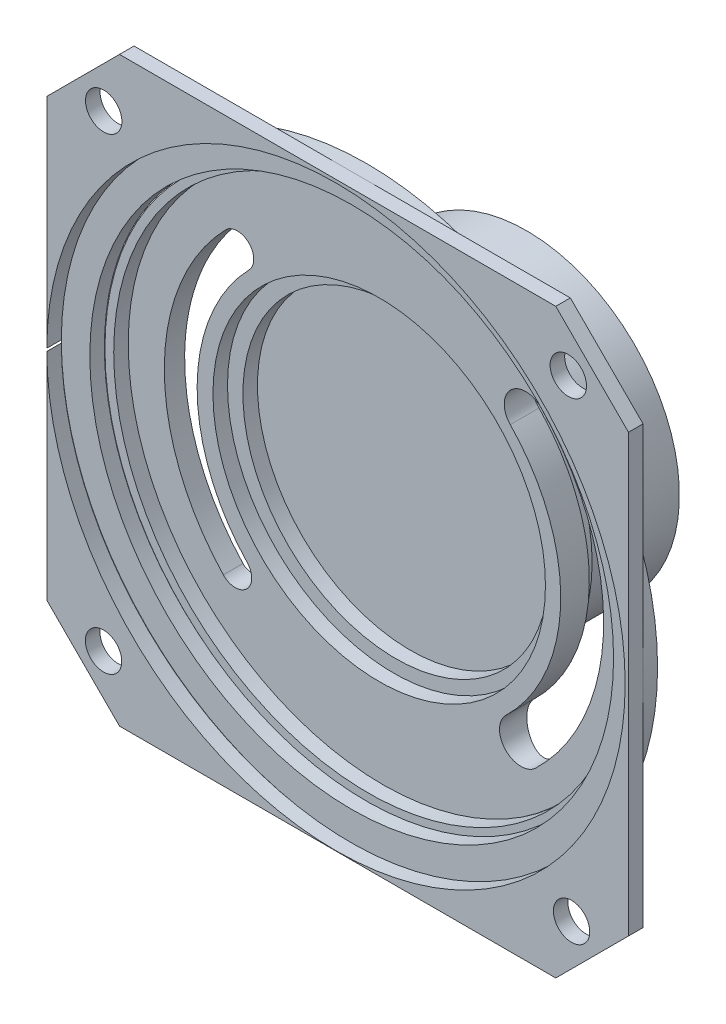
SolidWorks part; units mm, degrees
ref_plane "Front Plane" through (0, 0, 0) normal (0, 0, 1) x (1, 0, 0)
ref_plane "Top Plane" through (0, 0, 0) normal (0, 1, 0) x (1, 0, 0)
ref_plane "Right Plane" through (0, 0, 0) normal (1, 0, 0) x (0, 0, -1)
sketch "Sketch9" plane through (0, 0, 0) normal (0, 0, 1) x (1, 0, 0)
  line L0 (-18.0977, 3.7404) -> (-13.0977, 8.7404)
  line L1 (-13.0977, 8.7404) -> (16.9023, 8.7404)
  line L2 (-18.0977, 3.7404) -> (-18.0977, -26.2596)
  line L3 (-13.0977, -31.2596) -> (16.9023, -31.2596)
  line L4 (21.9023, 3.7404) -> (21.9023, -26.2596)
  line L5 (16.9023, 8.7404) -> (21.9023, 3.7404)
  line L6 (16.9023, -31.2596) -> (21.9023, -26.2596)
  line L7 (-18.0977, -26.2596) -> (-13.0977, -31.2596)
  circle A0 centre (1.9023, -11.2596) radius 20
  point P0 (-18.0977, 8.7404)
  point P1 (21.9023, -31.2596)
  point P2 (-18.0977, -31.2596)
  point P3 (21.9023, 8.7404)
  dimension "D3" = 40
  dimension "D1" = 40
  dimension "D2" = 40
extrude "Boss-Extrude8" add sketch "Sketch9" along normal blind 1 contours A0 L4 L5 L1 | A0 L3 L6 L4 | A0 | A0 L2 L7 L3 | A0 L1 L0 L2 region at (-13.153, 3.7957, 0) region at (-13.153, -26.3149, 0) region at (1.9023, -11.2596, 0) region at (16.9576, 3.7957, 0) region at (16.9576, -26.3149, 0)
sketch "Sketch10" plane through (0, 0, 0) normal (0, 0, -1) x (-1, 0, 0)
  circle A0 centre (-1.9023, -11.2596) radius 20
extrude "Boss-Extrude9" add sketch "Sketch10" along normal blind 1
sketch "Sketch11" plane through (0, 0, -1) normal (0, 0, -1) x (-1, 0, 0)
  circle A0 centre (-1.9023, -11.2596) radius 18
  circle A1 centre (-1.9023, -11.2596) radius 20 construction
  dimension "D1" = 2
extrude "Boss-Extrude10" add sketch "Sketch11" along normal blind 1
sketch "Sketch13" plane through (0, 0, -2) normal (0, 0, -1) x (-1, 0, 0)
  circle A0 centre (-1.9023, -11.2596) radius 17.5
  circle A1 centre (-1.9023, -11.2596) radius 18 construction
  point P4 (-1.9023, -11.2596)
  dimension "D1" = 0.5
extrude "Boss-Extrude11" add sketch "Sketch13" along normal blind 2
fillet "Fillet2" radius 10 1 edges at (-15.5977, -11.2596, -4)
sketch "Sketch15" plane through (0, 0, -4) normal (0, 0, -1) x (-1, 0, 0)
  circle A0 centre (-1.9023, -11.2596) radius 11.5
extrude "Boss-Extrude14" add sketch "Sketch15" along normal blind 1
sketch "Sketch16" plane through (0, 0, -5) normal (0, 0, -1) x (-1, 0, 0)
  circle A0 centre (-1.9023, -11.2596) radius 10.5
  circle A1 centre (-1.9023, -11.2596) radius 11.5 construction
  dimension "D1" = 1
extrude "Boss-Extrude15" add sketch "Sketch16" along normal blind 7
sketch "Sketch17" plane through (0, 0, 0) normal (0, 0, -1) x (-1, 0, 0)
  line L1 (-16.9023, 8.7404) -> (-21.9023, 3.7404) construction
  line L2 (18.0977, -26.2596) -> (13.0977, -31.2596) construction
  line L4 (18.0977, 3.7404) -> (13.0977, 8.7404) construction
  line L5 (-16.9023, -31.2596) -> (-21.9023, -26.2596) construction
  circle A0 centre (-17.9881, -27.3454) radius 1.25
  circle A1 centre (-17.7638, 5.0504) radius 1.25
  circle A2 centre (14.1835, 4.8261) radius 1.25
  circle A3 centre (14.1929, -27.336) radius 1.25
  dimension "D1" = 2.5
  dimension "D2" = 2.5
  dimension "D3" = 2.5
  dimension "D4" = 2.5
  dimension "D5" = 2
  dimension "D6" = 2
  dimension "D7" = 2
  dimension "D8" = 2
extrude "Cut-Extrude1" cut sketch "Sketch17" against normal blind 7
sketch "Sketch22" plane through (0, 0, 1) normal (0, 0, 1) x (1, 0, 0)
  circle A0 centre (1.7875, -11.3548) radius 19.8854
extrude "Cut-Extrude4" cut sketch "Sketch22" against normal blind 1
sketch "Sketch23" plane through (0, 0, 0) normal (0, 0, 1) x (1, 0, 0)
  circle A0 centre (1.87, -11.2317) radius 18.0067
extrude "Cut-Extrude5" cut sketch "Sketch23" against normal blind 1
sketch "Sketch24" plane through (0, 0, -1) normal (0, 0, 1) x (1, 0, 0)
  circle A0 centre (2.0036, -11.1941) radius 17.4988
extrude "Cut-Extrude6" cut sketch "Sketch24" against normal blind 1
sketch "Sketch25" plane through (0, 0, -2) normal (0, 0, 1) x (1, 0, 0)
  circle A0 centre (1.7603, -11.2511) radius 11.4316
extrude "Cut-Extrude7" cut sketch "Sketch25" against normal blind 1
sketch "Sketch31" plane through (0, 0, -2) normal (0, 0, 1) x (1, 0, 0)
  line L0 (21.9023, -11.2596) -> (-18.0977, -11.45) construction
  line L1 (1.9023, 8.7404) -> (1.9023, -31.2596) construction
  arc A0 (-8.1339, -20.9068) -> (-7.9924, -1.8453) centre (1.9023, -11.45) cw construction
  arc A1 (-8.8019, -1.0595) -> (-8.955, -21.6805) centre (1.9023, -11.45) ccw
  arc A2 (-7.1829, -2.631) -> (-7.3128, -20.1331) centre (1.9023, -11.45) ccw
  arc A3 (-7.1829, -2.631) -> (-8.8019, -1.0595) centre (-7.9924, -1.8453) ccw
  arc A4 (-8.955, -21.6805) -> (-7.3128, -20.1331) centre (-8.1339, -20.9068) ccw
  arc A5 (11.8334, -1.8453) -> (11.5071, -21.3811) centre (1.9023, -11.45) cw construction
  arc A6 (12.5328, -22.4418) -> (12.8941, -0.8195) centre (1.9023, -11.45) ccw
  arc A7 (10.4813, -20.3205) -> (10.7728, -2.871) centre (1.9023, -11.45) ccw
  arc A8 (10.4813, -20.3205) -> (12.5328, -22.4418) centre (11.5071, -21.3811) ccw
  arc A9 (12.8941, -0.8195) -> (10.7728, -2.871) centre (11.8334, -1.8453) ccw
  point P7 (-11.887, -11.3476)
  point P19 (15.7163, -11.6808)
extrude "Cut-Extrude8" cut sketch "Sketch31" against normal blind 3
sketch "Sketch32" plane through (0, 0, -3) normal (0, 0, 1) x (1, 0, 0)
  circle A0 centre (1.909, -11.2261) radius 10.5204
extrude "Cut-Extrude10" cut sketch "Sketch32" against normal blind 1
